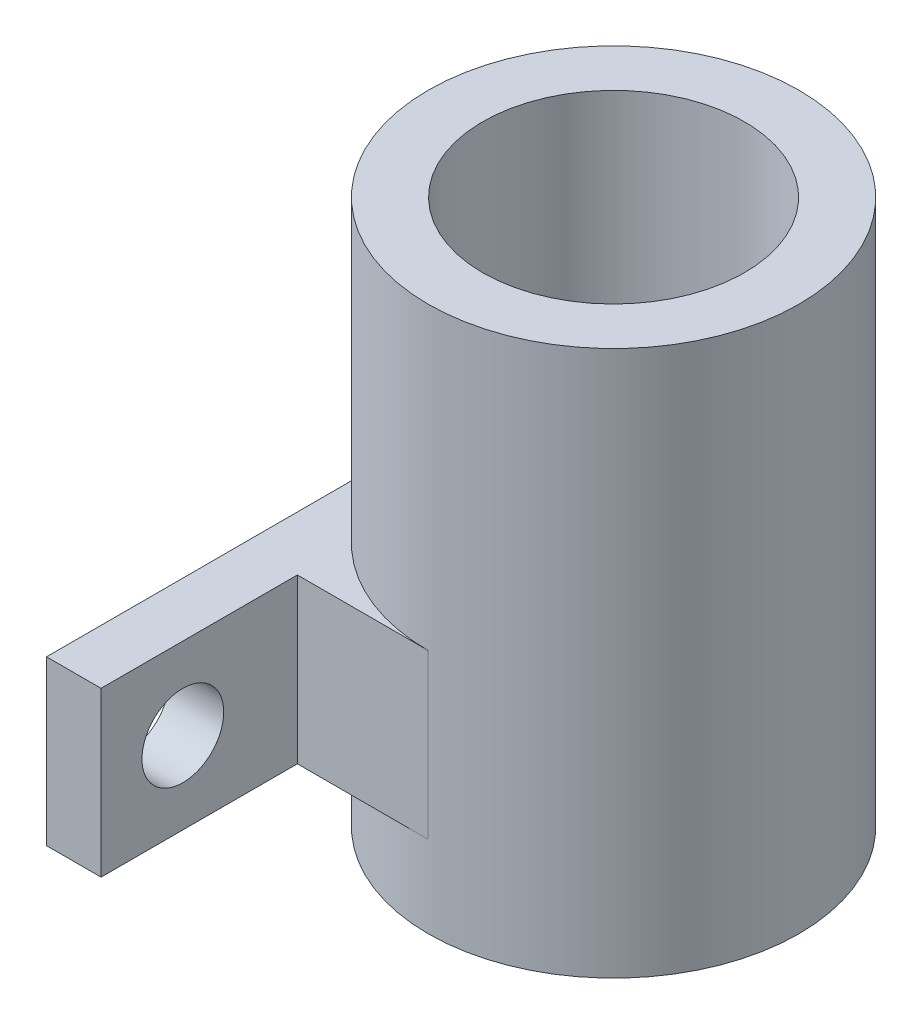
SolidWorks part; units mm, degrees
ref_plane "Front Plane" through (0, 0, 0) normal (0, 0, 1) x (1, 0, 0)
ref_plane "Top Plane" through (0, 0, 0) normal (0, 1, 0) x (1, 0, 0)
ref_plane "Right Plane" through (0, 0, 0) normal (1, 0, 0) x (0, 0, -1)
sketch "Sketch1" plane through (0, 0, 0) normal (0, 1, 0) x (1, 0, 0)
  circle A0 centre (0, 0) radius 4.8 construction
  circle A1 centre (0, 0) radius 6.8
  dimension "D1" = 9.6
  dimension "D2" = 13.6
extrude "Boss-Extrude1" add sketch "Sketch1" along normal blind 20 contours A1
sketch "Sketch3" plane through (0, 0, 0) normal (1, 0, 0) x (0, 0, -1)
  line L1 (6.8, 0) -> (6.8, 20) construction
  line L2 (6.8, 9) -> (-6.8, 9)
  line L3 (6.8, 9) -> (6.8, 3)
  line L4 (6.8, 3) -> (-6.8, 3)
  line L5 (-6.8, 9) -> (-6.8, 3)
  line L6 (6.8, 9) -> (-6.8, 3) construction
  line L7 (6.8, 3) -> (-6.8, 9) construction
  point P0 (0, 6)
  point P6 (0, 0)
  dimension "D1" = 6
  dimension "D3" = 6
extrude "Boss-Extrude3" add sketch "Sketch3" against normal blind 6.8 contours L2 L5 L4 L3
sketch "Sketch7" plane through (-6.8, 0, 0) normal (-1, 0, 0) x (0, 0, 1)
  line L1 (-14, 9) -> (14, 9)
  line L2 (-14, 9) -> (-14, 3)
  line L3 (-14, 3) -> (14, 3)
  line L4 (14, 9) -> (14, 3)
  line L5 (-14, 9) -> (14, 3) construction
  line L6 (-14, 3) -> (14, 9) construction
  line L7 (0, 9) -> (-6.8, 9) construction
  line L8 (-6.8, 3) -> (0, 3) construction
  point P0 (0, 6)
  point P5 (0, 0)
  point P10 (0, 0)
  dimension "D1" = 28
extrude "Boss-Extrude5" add sketch "Sketch7" against normal blind 2
sketch "Sketch8" plane through (-4.8, 0, 0) normal (1, 0, 0) x (0, 0, -1)
  line L0 (-14, 3) -> (-14, 9) construction
  circle A0 centre (-11, 6) radius 1.5
  point P4 (-14, 6)
  point P5 (-9.6598, 6)
  dimension "D1" = 3
  dimension "D2" = 3
extrude "Cut-Extrude2" cut sketch "Sketch8" against normal up to next
mirror "Mirror1" about plane through (0, 0, 0) normal (0, 0, 1) of "Cut-Extrude2"
sketch "Sketch2" plane through (0, 20, 0) normal (0, 1, 0) x (1, 0, 0)
  circle A0 centre (0, 0) radius 4.8
  circle A1 centre (0, 0) radius 6.8 construction
  dimension "D1" = 2
extrude "Cut-Extrude1" cut sketch "Sketch2" against normal offset from surface (18 mm away) 2 up to face at (0, 0, 6.8)
